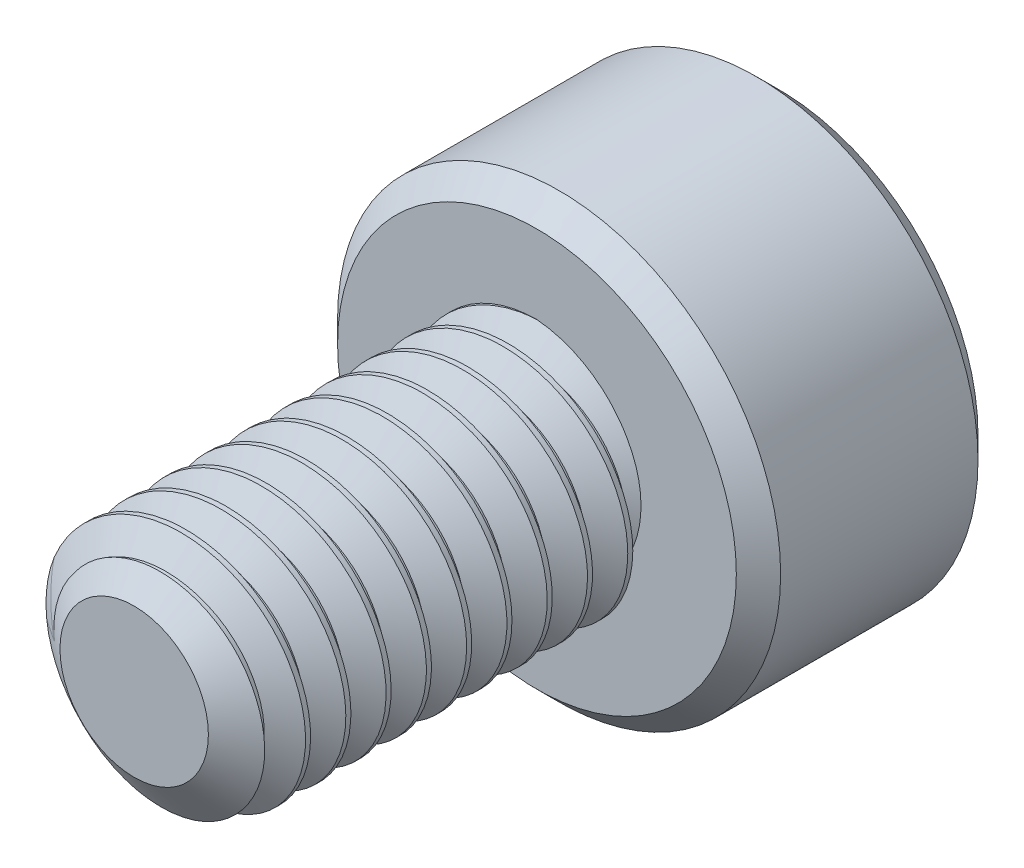
SolidWorks part; units mm, degrees
other "DetailItem1"
ref_plane "Front Plane" through (0, 0, 0) normal (0, 0, 1) x (1, 0, 0)
ref_plane "Top Plane" through (0, 0, 0) normal (0, 1, 0) x (1, 0, 0)
ref_plane "Right Plane" through (0, 0, 0) normal (1, 0, 0) x (0, 0, -1)
sketch "Sketch1" plane through (0, 0, 0) normal (0, 0, 1) x (1, 0, 0)
  circle A0 centre (0, 0) radius 1.5
  dimension "OD" = 3
extrude "Extrude1" add sketch "Sketch1" against normal blind 5
sketch "Sketch2" plane through (0, 0, 0) normal (0, 0, 1) x (1, 0, 0)
  circle A0 centre (0, 0) radius 1.5 construction
  circle A1 centre (0, 0) radius 1.5
curve "Helix/Spiral1" pitch 0.5 height 5.5 radius 1.5 centre (0, 0, 0) axis (0, 0, -1) start towards (0, 1, 0) parameters "pitch"=0.5
sketch "Sketch3" plane through (0, 0, 0) normal (1, 0, 0) x (0, 0, -1)
  line L0 (-0.4375, 1.5) -> (-0.25, 1.1752)
  line L1 (-0.25, 1.1752) -> (-0.1875, 1.1752)
  line L2 (-0.1875, 1.1752) -> (0, 1.5)
  line L3 (-0.4375, 1.5) -> (0, 1.5)
  line L4 (-0.2187, 1.5) -> (-0.2188, 1.1752) construction
  line L5 (-0.3438, 1.3376) -> (-0.0938, 1.3376) construction
  line L6 (0, 1.5) -> (0, -1.5) construction
  dimension "D1" = 0.0625
  dimension "D2" = 0.25
  dimension "D3" = 60
sweep "Cut-Sweep1" cut profiles "Sketch3" path "Helix/Spiral1"
sketch "Sketch4" plane through (0, 0, 0) normal (1, 0, 0) x (0, 0, -1)
  line L0 (0.4053, 1.5) -> (0, 0.9212)
  line L1 (0, 0.9212) -> (0, 1.5)
  line L2 (0.4053, 1.5) -> (0, 1.5)
  line L3 (-0.4375, 1.5) -> (0, 1.5) construction
  line L4 (0, 0) -> (7.0209, 0) construction
  dimension "D1" = 55
  dimension "D2" = 0.254
revolve "Cut-Revolve1" cut sketch "Sketch4" angle 360 about L4
sketch "Sketch6" plane through (0, 0, -5) normal (0, 0, -1) x (-1, 0, 0)
  circle A0 centre (0, 0) radius 2.75
  dimension "head dia" = 5.5
extrude "Extrude2" add sketch "Sketch6" along normal blind 3
sketch "Sketch7" plane through (0, 0, -8) normal (0, 0, -1) x (-1, 0, 0)
  line L1 (0, 1.4434) -> (-1.25, 0.7217)
  line L2 (-1.25, 0.7217) -> (-1.25, -0.7217)
  line L3 (-1.25, -0.7217) -> (0, -1.4434)
  line L4 (0, -1.4434) -> (1.25, -0.7217)
  line L5 (1.25, -0.7217) -> (1.25, 0.7217)
  line L6 (1.25, 0.7217) -> (0, 1.4434)
  circle A0 centre (0, 0) radius 1.25 construction
  dimension "hex dia" = 2.5
extrude "Cut-Extrude1" cut sketch "Sketch7" against normal blind 1.875
sketch "Sketch8" plane through (0, 0, -8) normal (0, 0, -1) x (-1, 0, 0)
  circle A0 centre (0, 0) radius 1.4434
extrude "Cut-Extrude2" cut sketch "Sketch8" against normal through all draft 45
chamfer "Chamfer1" distance 0.275 angle 45 2 edges at (-2.75, 0, -8) (-2.75, 0, -5)
sketch "Sketch10" plane through (0, 0, -5) normal (0, 0, 1) x (1, 0, 0)
  circle A1 centre (0, 0) radius 1.5
  circle A2 centre (0, 0) radius 1.5
  dimension "D1" = 0
ref_plane "Plane1" through (0, 0, 0) normal (0, 0, 1) x (1, 0, 0)
extrude "partial thread" [suppressed] add sketch "Sketch10" along normal up to surface (4 mm away) separate body up to plane "Plane1"
chamfer "Chamfer2" [suppressed] distance 0.06 angle 45
combine bodies "Combine1" [suppressed] operation type add bodies to combine 107 108
sketch "Sketch9" plane through (0, 0, 0) normal (1, 0, 0) x (0, 0, -1)
  line L0 (0, 1.5) -> (0, -1.5) construction
  line L1 (1.25, 1.5) -> (1.25, -1.5) construction
  dimension "D1" = 1.25
  dimension "D4" = 0.635
  dimension "D5" = 0.3302
equation "\"D3@Helix/Spiral1\" = \"screw length@Extrude1\"+\"pitch@Helix/Spiral1\""
equation "\"D1@Sketch3\" = \"pitch@Helix/Spiral1\"*.125"
equation "\"D2@Sketch3\" = \"pitch@Helix/Spiral1\"*.5"
equation "\"D1@Cut-Extrude1\" = \"hex dia@Sketch7\"*.75"
equation "\"D1@Chamfer1\" = \"head dia@Sketch6\"*.05"
equation "\"D1@Sketch9\" = \"pitch@Helix/Spiral1\"*2.5"
equation "\"D1@Chamfer2\"=\"OD@Sketch1\"*.02"
